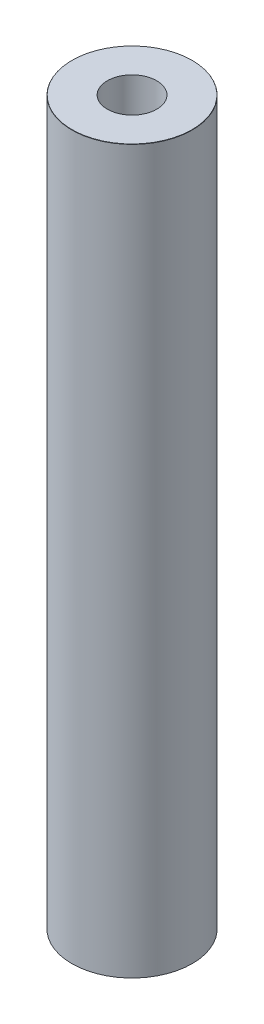
SolidWorks part; units mm, degrees
ref_plane "Front Plane" through (0, 0, 0) normal (0, 0, 1) x (1, 0, 0)
ref_plane "Top Plane" through (0, 0, 0) normal (0, 1, 0) x (1, 0, 0)
ref_plane "Right Plane" through (0, 0, 0) normal (1, 0, 0) x (0, 0, -1)
sketch "Sketch1" plane through (0, 0, 0) normal (0, 1, 0) x (1, 0, 0)
  circle A0 centre (0, 0) radius 50
  dimension "SHAFT_OD" = 100
extrude "Boss-Extrude1" add sketch "Sketch1" along normal blind 600
sketch "Sketch2" plane through (0, 0, 0) normal (0, 1, 0) x (1, 0, 0)
  circle A0 centre (0, 0) radius 20.517
  dimension "BORE_D" = 41.034
extrude "Cut-Extrude1" cut sketch "Sketch2" along normal through all
chamfer "Chamfer1" distance 0.2239 angle 29.028 2 edges at (0, 600, 50) (0, 0, 50) first distance on face at (0, 600, 50) first distance on face at (0, 0, 20.517)
